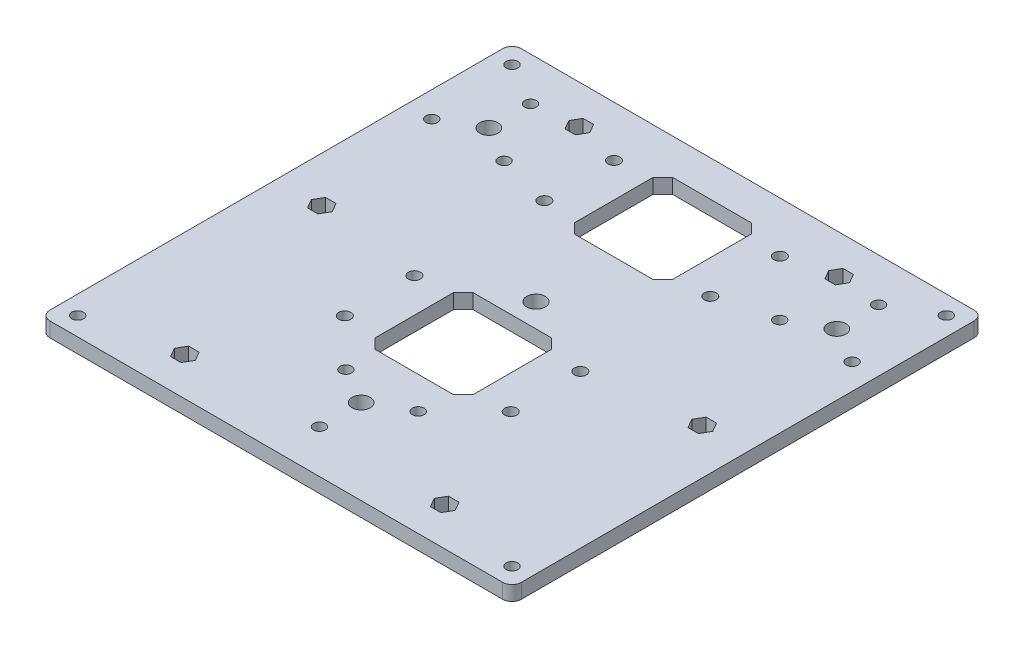
SolidWorks part; units mm, degrees
other "Marquage1"
sketch "Esquisse10" plane through (-101.6, 6.35, 101.6) normal (-0.0342, 0.9816, 0.1878) x (0.9994, 0.0344, 0.0025)
ref_plane "Plan de face" through (0, 0, 0) normal (0, 0, 1) x (1, 0, 0)
ref_plane "Plan de dessus" through (0, 0, 0) normal (0, 1, 0) x (1, 0, 0)
ref_plane "Plan de droite" through (0, 0, 0) normal (1, 0, 0) x (0, 0, -1)
sketch "Esquisse1" plane through (0, 0, 0) normal (0, 1, 0) x (1, 0, 0)
  line L1 (-101.6, -101.6) -> (101.6, -101.6)
  line L2 (-101.6, -101.6) -> (-101.6, 101.6)
  line L3 (-101.6, 101.6) -> (101.6, 101.6)
  line L4 (101.6, -101.6) -> (101.6, 101.6)
  line L5 (-101.6, -101.6) -> (101.6, 101.6) construction
  line L6 (-101.6, 101.6) -> (101.6, -101.6) construction
  point P0 (0, 0)
  dimension "D1" = 203.2
extrude "Boss.-Extru.1" add sketch "Esquisse1" along normal blind 6.35
sketch "Esquisse2" plane through (0, 6.35, 0) normal (0, 1, 0) x (1, 0, 0)
  circle A0 centre (-75, 65) radius 3.925
  circle A1 centre (75, 65) radius 3.925
  circle A2 centre (0, -65) radius 3.925
  dimension "D1" = 7.85
  dimension "D2" = 65
  dimension "D3" = 65
  dimension "D4" = 150
  dimension "D5" = 75
extrude "Enlèv. mat.-Extru.1" cut sketch "Esquisse2" against normal through all
sketch "Esquisse3" plane through (0, 6.35, 0) normal (0, 1, 0) x (1, 0, 0)
  line L0 (-16.9781, 86.15) -> (-21.15, 81.9781)
  line L1 (-21.15, 81.9781) -> (-21.15, 48.0219)
  line L2 (-21.15, 48.0219) -> (-16.9781, 43.85)
  line L3 (-16.9781, 43.85) -> (16.9781, 43.85)
  line L4 (16.9781, 43.85) -> (21.15, 48.0219)
  line L5 (21.15, 48.0219) -> (21.15, 81.9781)
  line L6 (21.15, 81.9781) -> (16.9781, 86.15)
  line L7 (16.9781, 86.15) -> (-16.9781, 86.15)
  line L9 (-75, 65) -> (75, 65) construction
  point P8 (0, 43.85)
  point P11 (0, 86.15)
  point P12 (-21.15, 65)
  point P13 (21.15, 65)
  dimension "D1" = 5.9
  dimension "D2" = 42.3
extrude "Enlèv. mat.-Extru.2" cut sketch "Esquisse3" against normal through all
sketch "Esquisse5" plane through (0, 6.35, 0) normal (0, 1, 0) x (1, 0, 0)
  circle A0 centre (-35.9, 49.85) radius 2.6
  circle A1 centre (-35.9, 79.85) radius 2.6
  circle A2 centre (35.6, 49.85) radius 2.6
  circle A3 centre (35.6, 79.85) radius 2.6
  circle A4 centre (35.6, 49.85) radius 2.6 construction
extrude "Enlèv. mat.-Extru.4" cut sketch "Esquisse5" against normal through all
sketch "Esquisse6" plane through (0, 6.35, 0) normal (0, 1, 0) x (1, 0, 0)
  line L0 (-101.6, -101.6) -> (101.6, -101.6) construction
  line L1 (101.6, -101.6) -> (101.6, 101.6) construction
  line L2 (-101.6, 101.6) -> (-101.6, -101.6) construction
  line L3 (101.6, 101.6) -> (-101.6, 101.6) construction
  circle A0 centre (93.6, -93.6) radius 2.5
  circle A1 centre (-93.6, -93.6) radius 2.5
  circle A2 centre (-93.6, 93.6) radius 2.5
  circle A3 centre (93.6, 93.6) radius 2.5
  dimension "D1" = 5
  dimension "D2" = 8
  dimension "D3" = 8
  dimension "D4" = 8
  dimension "D5" = 8
extrude "Enlèv. mat.-Extru.5" cut sketch "Esquisse6" against normal through all
sketch "Esquisse7" plane through (0, 6.35, 0) normal (0, 1, 0) x (1, 0, 0)
  circle A0 centre (15.5885, -56) radius 2.5
  circle A1 centre (-15.5885, -56) radius 2.5
  circle A2 centre (0, -83) radius 2.5
  circle A3 centre (90.5885, 56) radius 2.5
  circle A4 centre (59.4115, 56) radius 2.5
  circle A5 centre (75, 83) radius 2.5
  circle A6 centre (-90.5899, 55.9992) radius 2.5
  circle A7 centre (-59.413, 55.9992) radius 2.5
  circle A8 centre (-75.0015, 82.9992) radius 2.5
extrude "Enlèv. mat.-Extru.6" cut sketch "Esquisse7" against normal through all
sketch "Esquisse8" plane through (0, 6.35, 0) normal (0, 1, 0) x (1, 0, 0)
  circle A0 centre (0, 10.325) radius 4
  circle A1 centre (0, 10.325) radius 4 construction
extrude "Enlèv. mat.-Extru.7" cut sketch "Esquisse8" against normal through all
sketch "Esquisse9" plane through (0, 0, 0) normal (0, -1, 0) x (1, 0, 0)
  circle A0 centre (56, -85) radius 2.5
  circle A1 centre (56, -85) radius 2.5 construction
  circle A2 centre (82, 0) radius 2.5
  circle A3 centre (82, 0) radius 2.5 construction
extrude "Enlèv. mat.-Extru.8" cut sketch "Esquisse9" against normal through all
mirror "Symétrie1" about plane through (0, 0, 0) normal (0, 0, 1) of "Enlèv. mat.-Extru.8"
mirror "Symétrie2" about plane through (0, 0, 0) normal (1, 0, 0) of "Symétrie1"
sketch "Esquisse11" plane through (0, 0, 0) normal (0, -1, 0) x (1, 0, 0)
  line L0 (-97.6, 101.6) -> (97.6, 101.6) construction
  line L1 (-60.5033, -85) -> (-58.2517, -88.9)
  line L2 (-58.2517, -88.9) -> (-53.7483, -88.9)
  line L3 (-53.7483, -88.9) -> (-51.4967, -85)
  line L4 (-51.4967, -85) -> (-53.7483, -81.1)
  line L5 (-53.7483, -81.1) -> (-58.2517, -81.1)
  line L6 (-58.2517, -81.1) -> (-60.5033, -85)
  line L7 (-86.5033, 0) -> (-84.2517, -3.9)
  line L8 (-84.2517, -3.9) -> (-79.7483, -3.9)
  line L9 (-79.7483, -3.9) -> (-77.4967, 0)
  line L10 (-77.4967, 0) -> (-79.7483, 3.9)
  line L11 (-79.7483, 3.9) -> (-84.2517, 3.9)
  line L12 (-84.2517, 3.9) -> (-86.5033, 0)
  line L13 (-60.5033, 85) -> (-58.2517, 81.1)
  line L14 (-58.2517, 81.1) -> (-53.7483, 81.1)
  line L15 (-53.7483, 81.1) -> (-51.4967, 85)
  line L16 (-51.4967, 85) -> (-53.7483, 88.9)
  line L17 (-53.7483, 88.9) -> (-58.2517, 88.9)
  line L18 (-58.2517, 88.9) -> (-60.5033, 85)
  line L19 (51.4967, 85) -> (53.7483, 81.1)
  line L20 (53.7483, 81.1) -> (58.2517, 81.1)
  line L21 (58.2517, 81.1) -> (60.5033, 85)
  line L22 (60.5033, 85) -> (58.2517, 88.9)
  line L23 (58.2517, 88.9) -> (53.7483, 88.9)
  line L24 (53.7483, 88.9) -> (51.4967, 85)
  line L25 (77.4967, 0) -> (79.7483, -3.9)
  line L26 (79.7483, -3.9) -> (84.2517, -3.9)
  line L27 (84.2517, -3.9) -> (86.5033, 0)
  line L28 (86.5033, 0) -> (84.2517, 3.9)
  line L29 (84.2517, 3.9) -> (79.7483, 3.9)
  line L30 (79.7483, 3.9) -> (77.4967, 0)
  line L31 (60.5033, -85) -> (58.2517, -81.1)
  line L32 (58.2517, -81.1) -> (53.7483, -81.1)
  line L33 (53.7483, -81.1) -> (51.4967, -85)
  line L34 (51.4967, -85) -> (53.7483, -88.9)
  line L35 (53.7483, -88.9) -> (58.2517, -88.9)
  line L36 (58.2517, -88.9) -> (60.5033, -85)
  circle A0 centre (-56, -85) radius 3.9 construction
  circle A1 centre (-82, 0) radius 3.9 construction
  circle A2 centre (-56, 85) radius 3.9 construction
  circle A3 centre (56, 85) radius 3.9 construction
  circle A4 centre (82, 0) radius 3.9 construction
  circle A5 centre (56, -85) radius 3.9 construction
extrude "Enlèv. mat.-Extru.9" cut sketch "Esquisse11" against normal through all
fillet "Congé1" radius 4 4 edges at (-101.6, 3.175, -101.6) (101.6, 3.175, -101.6) (101.6, 3.175, 101.6) (-101.6, 3.175, 101.6)
sketch "Esquisse12" plane through (0, 6.35, 0) normal (0, 1, 0) x (1, 0, 0)
  circle A0 centre (-0.0005, -21) radius 5.7
  circle A1 centre (-0.0005, -21) radius 5.7 construction
sketch "Esquisse13" plane through (0, 6.35, 0) normal (0, 1, 0) x (1, 0, 0)
  line L0 (-16.9781, 0.15) -> (16.9781, 0.15)
  line L1 (16.9781, 0.15) -> (21.15, -4.0219)
  line L2 (21.15, -4.0219) -> (21.15, -37.9781)
  line L3 (21.15, -37.9781) -> (16.9781, -42.15)
  line L4 (16.9781, -42.15) -> (-16.9781, -42.15)
  line L5 (-16.9781, -42.15) -> (-21.15, -37.9781)
  line L6 (-21.15, -37.9781) -> (-21.15, -4.0219)
  line L7 (-21.15, -4.0219) -> (-16.9781, 0.15)
  point P7 (21.15, -21)
  point P9 (-21.15, -21)
  point P11 (0, 0.15)
  point P12 (0, -42.15)
  dimension "D1" = 5.9
  dimension "D2" = 42.3
  dimension "D3" = 42.3
extrude "Enlèv. mat.-Extru.10" cut sketch "Esquisse13" against normal through all
pattern_linear "Répétition linéaire3" count 2 spacing 86 along (0, 0, 1) of "Enlèv. mat.-Extru.4"
